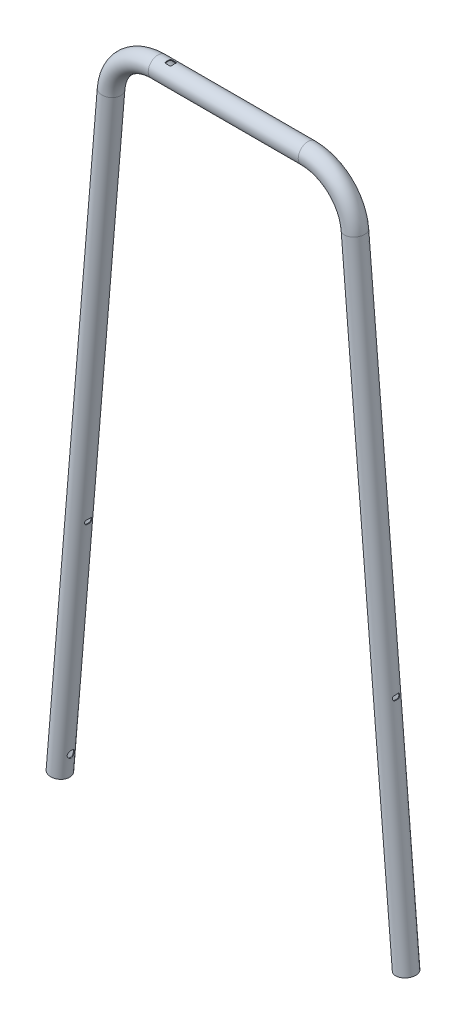
SolidWorks part; units mm, degrees
ref_plane "Front Plane" through (0, 0, 0) normal (0, 0, 1) x (1, 0, 0)
ref_plane "Top Plane" through (0, 0, 0) normal (0, 1, 0) x (1, 0, 0)
ref_plane "Right Plane" through (0, 0, 0) normal (1, 0, 0) x (0, 0, -1)
sketch "Sketch1" plane through (0, 0, 0) normal (0, 0, 1) x (1, 0, 0)
  line L0 (0, 0) -> (0, 595.2821) construction
  line L1 (0, 0) -> (414.971, 0) construction
  line L2 (-84.4159, 579.716) -> (84.4159, 579.716)
  line L3 (137.2338, 531.1048) -> (194.85, -162.284)
  line L4 (-137.2338, 531.1048) -> (-194.85, -162.284)
  line L5 (-194.85, -162.284) -> (-299.6948, -162.284) construction
  arc A0 (137.2338, 531.1048) -> (84.4159, 579.716) centre (84.4159, 526.716) ccw
  arc A1 (-137.2338, 531.1048) -> (-84.4159, 579.716) centre (-84.4159, 526.716) cw
  point P12 (133.1946, 579.716)
  point P17 (0, 579.716)
  dimension "D4" = 53
  dimension "D1" = 389.7
  dimension "D2" = 85.25
  dimension "D3" = 742
ref_plane "Plane1" through (-194.85, -162.284, 0) normal (-0.0828, -0.9966, 0) x (-0.9966, 0.0828, 0)
sketch "Sketch2" plane through (-194.85, -162.284, 0) normal (-0.0828, -0.9966, 0) x (-0.9966, 0.0828, 0)
  circle A0 centre (0, 0) radius 11
  circle A1 centre (0, 0) radius 10.2
  dimension "D1" = 0.8
sweep "Sweep2" add profiles "Sketch2" path "Sketch1"
sketch "Sketch6" plane through (-14.7284, -177.251, 0) normal (-0.0828, -0.9966, 0) x (0.9966, -0.0828, 0)
  line L0 (-180.7423, 0) -> (-190.9423, 0)
  line L1 (-180.7423, 0) -> (-180.7423, 10.2)
  circle A0 centre (-180.7423, 0) radius 10.2 construction
  circle A1 centre (-180.7423, 0) radius 10.2 construction
ref_plane "Plane3" through (-194.85, -162.284, 0) normal (-0.9966, 0.0828, 0) x (0, 0, 1)
ref_plane "Plane4" through (0, 590.716, 0) normal (0, 1, 0) x (1, 0, 0)
sketch "Sketch17" plane through (-194.85, -162.284, 0) normal (-0.9966, 0.0828, 0) x (0, 0, 1)
  line L0 (0, 0) -> (0, 23.8) construction
  line L1 (-11, 0) -> (11, 0) construction
  line L2 (0, 23.8) -> (0, 236.8) construction
  circle A0 centre (0, 23.8) radius 4
  dimension "D3" = 8
  dimension "D1" = 23.8
  dimension "D2" = 236.8
extrude "Cut-Extrude6" cut sketch "Sketch17" against normal blind 50
sketch "Sketch18" plane through (-194.85, -162.284, 0) normal (-0.9966, 0.0828, 0) x (0, 0, 1)
  line L0 (0, 0) -> (0, 261.3035) construction
  line L1 (-10.2, 0) -> (10.2, 0) construction
  line L3 (-2, 263.8035) -> (2, 263.8035)
  line L4 (-4, 261.8035) -> (-4, 260.8035)
  line L5 (-2, 258.8035) -> (2, 258.8035)
  line L6 (4, 261.8035) -> (4, 260.8035)
  line L7 (-4, 263.8035) -> (4, 258.8035) construction
  line L8 (-4, 258.8035) -> (4, 263.8035) construction
  arc A0 (-2, 258.8035) -> (-4, 260.8035) centre (-2, 260.8035) cw
  arc A1 (4, 260.8035) -> (2, 258.8035) centre (2, 260.8035) cw
  arc A2 (2, 263.8035) -> (4, 261.8035) centre (2, 261.8035) cw
  arc A3 (-2, 263.8035) -> (-4, 261.8035) centre (-2, 261.8035) ccw
  dimension "D3" = 2
  dimension "D1" = 5
  dimension "D2" = 8
  dimension "D4" = 5
extrude "Cut-Extrude7" cut sketch "Sketch18" against normal blind 50 and the other way blind 50
mirror "Mirror2" about plane through (0, 0, 0) normal (1, 0, 0) of "Cut-Extrude6", "Cut-Extrude7"
sketch "Sketch19" plane through (-194.85, -162.284, 0) normal (-0.9966, 0.0828, 0) x (0, 0, 1)
  line L0 (0, 0) -> (0, 496.8) construction
  line L1 (-10.2, 0) -> (10.2, 0) construction
  circle A0 centre (0, 496.8) radius 4
  dimension "D1" = 496.8
extrude "Cut-Extrude8" cut sketch "Sketch19" along normal blind 50
sketch "Sketch20" plane through (0, 590.716, 0) normal (0, 1, 0) x (1, 0, 0)
  line L0 (-205.8122, 0) -> (-69.9338, 0) construction
  circle A0 centre (-69.9338, 0) radius 3.5
  ellipse E0 centre (-194.85, 0) end of major axis (-194.85, 11) minor radius 10.9622 construction
  ellipse E1 centre (-137.2338, 0) end of major axis (-137.2338, 11) minor radius 10.9622 construction
  dimension "D2" = 7
  dimension "D1" = 67.3
extrude "Cut-Extrude9" cut sketch "Sketch20" against normal blind 50
sketch "Sketch21" plane through (0, 590.716, 0) normal (0, 1, 0) x (1, 0, 0)
  line L0 (-205.8122, 0) -> (-69.9338, 0) construction
  line L2 (-72.4338, -3.5) -> (-67.4338, -3.5)
  line L3 (-73.4338, -2.5) -> (-73.4338, 2.5)
  line L4 (-72.4338, 3.5) -> (-67.4338, 3.5)
  line L5 (-66.4338, -2.5) -> (-66.4338, 2.5)
  line L6 (-73.4338, -3.5) -> (-66.4338, 3.5) construction
  line L7 (-73.4338, 3.5) -> (-66.4338, -3.5) construction
  arc A0 (-72.4338, 3.5) -> (-73.4338, 2.5) centre (-72.4338, 2.5) ccw
  arc A1 (-73.4338, -2.5) -> (-72.4338, -3.5) centre (-72.4338, -2.5) ccw
  arc A2 (-67.4338, 3.5) -> (-66.4338, 2.5) centre (-67.4338, 2.5) cw
  arc A3 (-66.4338, -2.5) -> (-67.4338, -3.5) centre (-67.4338, -2.5) cw
  ellipse E0 centre (-194.85, 0) end of major axis (-194.85, 11) minor radius 10.9622 construction
  dimension "D3" = 1
  dimension "D4" = 1
  dimension "D1" = 7
  dimension "D2" = 7
extrude "Cut-Extrude10" cut sketch "Sketch21" against normal blind 10
